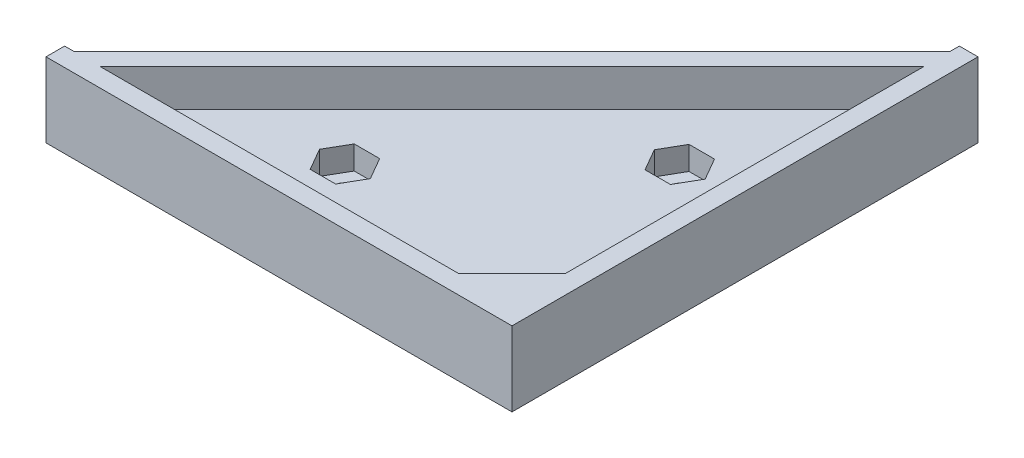
SolidWorks part; units mm, degrees
ref_plane "Front Plane" through (0, 0, 0) normal (0, 0, 1) x (1, 0, 0)
ref_plane "Top Plane" through (0, 0, 0) normal (0, 1, 0) x (1, 0, 0)
ref_plane "Right Plane" through (0, 0, 0) normal (1, 0, 0) x (0, 0, -1)
sketch "Sketch1" plane through (0, 0, 0) normal (0, 1, 0) x (1, 0, 0)
  line L0 (-79.375, 0) -> (0, 0)
  line L1 (0, 0) -> (0, 79.375)
  line L2 (0, 79.375) -> (-3.175, 79.375)
  line L3 (-3.175, 79.375) -> (-3.175, 77.7875)
  line L4 (-3.175, 77.7875) -> (-77.7875, 3.175)
  line L5 (-77.7875, 3.175) -> (-79.375, 3.175)
  line L6 (-79.375, 3.175) -> (-79.375, 0)
  dimension "D1" = 76.2
  dimension "D2" = 79.375
  dimension "D3" = 3.175
  dimension "D4" = 1.5875
extrude "Boss-Extrude1" add sketch "Sketch1" along normal blind 12.7
sketch "Sketch2" plane through (0, 12.7, 0) normal (0, 1, 0) x (1, 0, 0)
  line L0 (-73.2974, 3.175) -> (-12.2411, 3.175)
  line L1 (-3.175, 12.2411) -> (-3.175, 73.2974)
  line L2 (-3.175, 73.2974) -> (-73.2974, 3.175)
  line L3 (-12.2411, 3.175) -> (-3.175, 12.2411)
  line L5 (-79.375, 0) -> (0, 0) construction
  line L6 (0, 0) -> (0, 79.375) construction
  line L7 (-3.175, 77.7875) -> (-77.7875, 3.175) construction
  dimension "D2" = 3.175
  dimension "D3" = 3.175
  dimension "D4" = 3.175
extrude "Cut-Extrude1" cut sketch "Sketch2" against normal blind 6.35
chamfer "Chamfer1" distance 6.35 angle 45 1 edges at (-7.708, 6.35, -7.708)
sketch "Sketch3" plane through (0, 6.35, 0) normal (0, 1, 0) x (1, 0, 0)
  line L0 (-79.375, 0) -> (0, 0) construction
  line L1 (0, 0) -> (0, 79.375) construction
  circle A0 centre (-44.4608, 16.002) radius 1.75
  circle A1 centre (-15.875, 44.45) radius 1.75
  dimension "D1" = 3.5
  dimension "D2" = 3.5
  dimension "D3" = 16.002
  dimension "D4" = 44.4608
  dimension "D5" = 15.875
  dimension "D6" = 44.45
extrude "Cut-Extrude2" cut sketch "Sketch3" against normal blind 6.35
sketch "Sketch4" plane through (0, 6.35, 0) normal (0, 1, 0) x (1, 0, 0)
  line L1 (-13.7099, 40.7) -> (-11.5449, 44.45)
  line L2 (-11.5449, 44.45) -> (-13.7099, 48.2)
  line L3 (-13.7099, 48.2) -> (-18.0401, 48.2)
  line L4 (-18.0401, 48.2) -> (-20.2051, 44.45)
  line L5 (-20.2051, 44.45) -> (-18.0401, 40.7)
  line L6 (-18.0401, 40.7) -> (-13.7099, 40.7)
  line L7 (-40.1307, 16.002) -> (-42.2957, 19.752)
  line L8 (-42.2957, 19.752) -> (-46.6259, 19.752)
  line L9 (-46.6259, 19.752) -> (-48.7909, 16.002)
  line L10 (-48.7909, 16.002) -> (-46.6259, 12.252)
  line L11 (-46.6259, 12.252) -> (-42.2957, 12.252)
  line L12 (-42.2957, 12.252) -> (-40.1307, 16.002)
  circle A0 centre (-44.4608, 16.002) radius 1.75 construction
  circle A1 centre (-15.875, 44.45) radius 1.75 construction
  circle A2 centre (-44.4608, 16.002) radius 1.75
  circle A3 centre (-15.875, 44.45) radius 1.75
  circle A4 centre (-15.875, 44.45) radius 3.75 construction
  circle A5 centre (-44.4608, 16.002) radius 3.75 construction
  dimension "D1" = 7.5
  dimension "D2" = 7.5
extrude "Cut-Extrude3" cut sketch "Sketch4" against normal blind 4
